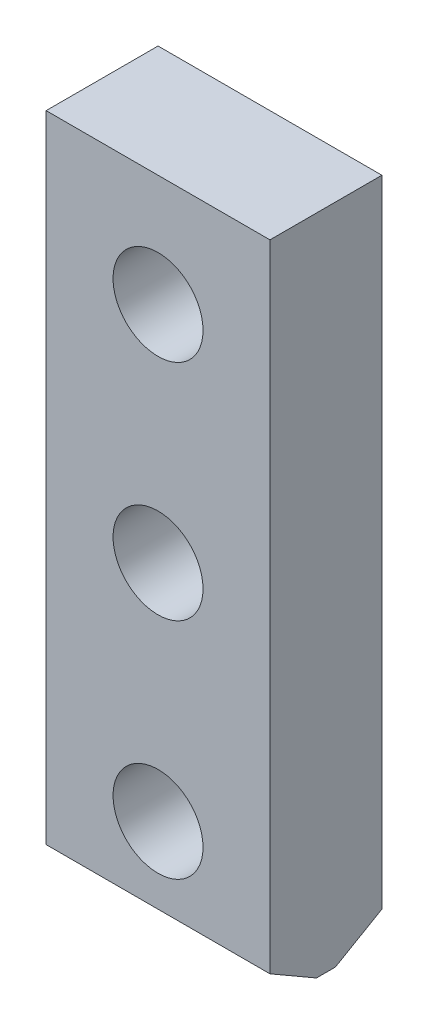
SolidWorks part; units mm, degrees
ref_plane "Спереди" through (0, 0, 0) normal (0, 0, 1) x (1, 0, 0)
ref_plane "Сверху" through (0, 0, 0) normal (0, 1, 0) x (1, 0, 0)
ref_plane "Справа" through (0, 0, 0) normal (1, 0, 0) x (0, 0, -1)
sketch "Эскиз1" plane through (0, 0, 0) normal (0, 0, 1) x (1, 0, 0)
  line L1 (0, 0) -> (50, 0)
  line L2 (0, 0) -> (0, 148)
  line L3 (0, 148) -> (50, 148)
  line L4 (50, 0) -> (50, 148)
  point P5 (25, 148)
  dimension "D1" = 148
  dimension "D2" = 50
extrude "Бобышка-Вытянуть1" add sketch "Эскиз1" along normal blind 25
sketch "Эскиз2" plane through (0, 0, 25) normal (0, 0, 1) x (1, 0, 0)
  line L0 (0, 0) -> (50, 0) construction
  line L1 (50, 0) -> (50, 148) construction
  circle A0 centre (25, 23) radius 10.05
  circle A1 centre (25, 73) radius 10.05
  circle A2 centre (25, 123) radius 10.05
  dimension "D1" = 3
  dimension "D2" = 23
  dimension "D3" = 25
  dimension "D4" = 20.1
extrude "Вырез-Вытянуть1" cut sketch "Эскиз2" against normal through all
chamfer "Фаска1" distance 6 angle 60 1 edges at (25, 0, 0) first distance on face at (35.05, 73, 0)
chamfer "Фаска2" distance 6 angle 60 1 edges at (25, 0, 25) first distance on face at (35.05, 73, 25)
